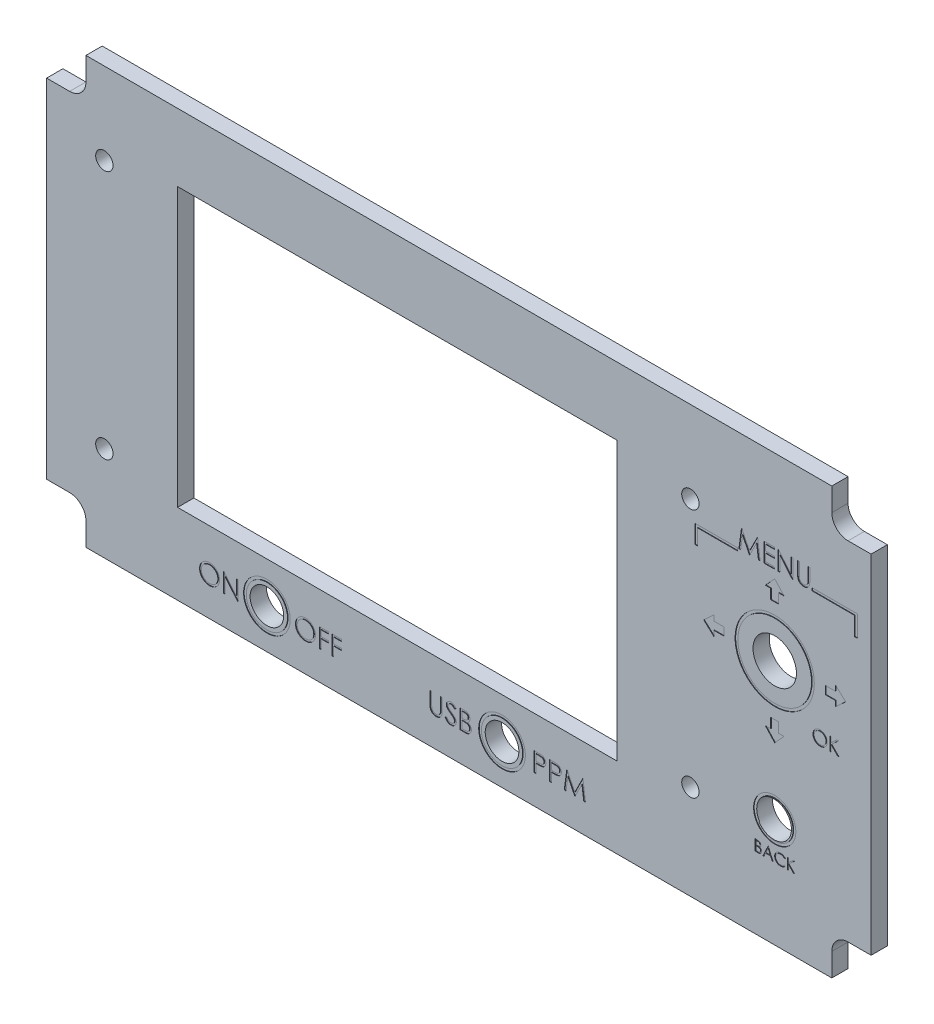
SolidWorks part; units mm, degrees
ref_plane "Plan de face" through (0, 0, 0) normal (0, 0, 1) x (1, 0, 0)
ref_plane "Plan de dessus" through (0, 0, 0) normal (0, 1, 0) x (1, 0, 0)
ref_plane "Plan de droite" through (0, 0, 0) normal (1, 0, 0) x (0, 0, -1)
sketch "Esquisse1" plane through (0, 0, 3.8) normal (0, 0, 1) x (1, 0, 0)
  line L0 (-95.6944, -23.7786) -> (-14.6944, -23.7786) construction
  line L1 (-14.6944, -23.7786) -> (-14.6944, 27.4214) construction
  line L2 (-108.6086, -31.3167) -> (5.0728, -31.3167) construction
  line L3 (-95.6944, 27.4214) -> (-95.6944, -23.7786) construction
  line L4 (-95.6944, -23.7786) -> (-14.6944, -23.7786)
  line L5 (-14.6944, -23.7786) -> (-14.6944, 27.4214)
  line L6 (-14.6944, 27.4214) -> (-95.6944, 27.4214)
  line L7 (-95.6944, 27.4214) -> (-95.6944, -23.7786)
  line L12 (32.1075, 39.9055) -> (-119.8323, 39.9055) construction
  line L13 (32.1075, -38.6114) -> (32.1075, 39.9055) construction
  line L15 (-119.8323, 39.9055) -> (-119.8323, -38.6114) construction
  line L24 (-115.5896, 32.6629) -> (-119.8323, 32.6629)
  line L25 (-119.8323, 32.6629) -> (-119.8323, -31.3687)
  line L26 (-119.8323, -31.3687) -> (-115.5896, -31.3687)
  line L27 (-112.5896, -34.3687) -> (-112.5896, -38.6114)
  line L28 (-112.5896, -38.6114) -> (24.8649, -38.6114)
  line L29 (24.8649, -38.6114) -> (24.8649, -34.3687)
  line L30 (27.8649, -31.3687) -> (32.1075, -31.3687)
  line L31 (32.1075, -31.3687) -> (32.1075, 32.6629)
  line L32 (32.1075, 32.6629) -> (27.8649, 32.6629)
  line L33 (24.8649, 35.6629) -> (24.8649, 39.9055)
  line L34 (24.8649, 39.9055) -> (-112.5896, 39.9055)
  line L35 (-112.5896, 39.9055) -> (-112.5896, 35.6629)
  circle A0 centre (-35.9056, -31.3167) radius 3.1
  circle A1 centre (-1.1944, 24.8214) radius 1.6
  circle A2 centre (-109.1944, 24.8214) radius 1.6
  circle A3 centre (-109.1944, -21.1786) radius 1.6
  circle A4 centre (-79.2375, -31.3167) radius 3.1
  circle A5 centre (-1.1944, -21.1786) radius 1.6
  circle A6 centre (-109.1944, 24.8214) radius 2 construction
  circle A7 centre (-1.1944, 24.8214) radius 2 construction
  arc A8 (-115.5896, 32.6629) -> (-112.5896, 35.6629) centre (-115.5896, 35.6629) ccw
  arc A9 (-112.5896, -34.3687) -> (-115.5896, -31.3687) centre (-115.5896, -34.3687) ccw
  arc A10 (27.8649, -31.3687) -> (24.8649, -34.3687) centre (27.8649, -34.3687) ccw
  arc A11 (24.8649, 35.6629) -> (27.8649, 32.6629) centre (27.8649, 35.6629) ccw
  circle A12 centre (-1.1944, -21.1786) radius 2 construction
  circle A13 centre (-109.1944, -21.1786) radius 2 construction
  circle A28 centre (14.3452, 6.7499) radius 4
  circle A45 centre (14.1766, -18.6114) radius 3.25
  dimension "D2" = 6.5
  dimension "D1" = 6.2
extrude "Boss.-Extru.1" add sketch "Esquisse1" along normal blind 3
sketch "Gravure" plane through (0, 0, 6.8) normal (0, 0, 1) x (1, 0, 0)
  line L0 (-0.3763, 21.3599) -> (-0.3763, 17.9616)
  line L1 (14.3452, 6.7499) -> (14.3452, 16.1393) construction
  line L2 (13.6084, 16.1393) -> (15.082, 16.1393)
  line L3 (13.6084, 16.1393) -> (13.6084, 17.9616)
  line L4 (13.6084, 17.9616) -> (12.6237, 17.9616)
  line L5 (12.6237, 17.9616) -> (14.3452, 19.8356)
  line L6 (14.3452, 19.8356) -> (16.0668, 17.9616)
  line L7 (16.0668, 17.9616) -> (15.082, 17.9616)
  line L8 (15.082, 17.9616) -> (15.082, 16.1393)
  line L9 (14.3452, 6.7499) -> (17.3937, 6.7499) construction
  line L10 (25.557, 6.013) -> (23.7347, 6.013)
  line L11 (25.557, 5.0283) -> (25.557, 6.013)
  line L12 (27.431, 6.7499) -> (25.557, 5.0283)
  line L13 (25.557, 8.4714) -> (27.431, 6.7499)
  line L14 (25.557, 7.4867) -> (25.557, 8.4714)
  line L15 (23.7347, 7.4867) -> (25.557, 7.4867)
  line L16 (23.7347, 7.4867) -> (23.7347, 6.013)
  line L17 (13.6084, -4.4619) -> (13.6084, -2.6396)
  line L18 (12.6237, -4.4619) -> (13.6084, -4.4619)
  line L19 (14.3452, -6.3359) -> (12.6237, -4.4619)
  line L20 (16.0668, -4.4619) -> (14.3452, -6.3359)
  line L21 (15.082, -4.4619) -> (16.0668, -4.4619)
  line L22 (15.082, -2.6396) -> (15.082, -4.4619)
  line L23 (15.082, -2.6396) -> (13.6084, -2.6396)
  line L24 (3.1335, 7.4867) -> (4.9558, 7.4867)
  line L25 (3.1335, 8.4714) -> (3.1335, 7.4867)
  line L26 (1.2595, 6.7499) -> (3.1335, 8.4714)
  line L27 (3.1335, 5.0283) -> (1.2595, 6.7499)
  line L28 (3.1335, 6.013) -> (3.1335, 5.0283)
  line L29 (4.9558, 6.013) -> (3.1335, 6.013)
  line L30 (4.9558, 6.013) -> (4.9558, 7.4867)
  line L31 (14.3452, 6.7499) -> (14.3452, -18.6114) construction
  line L32 (7.4858, 21.3599) -> (21.2046, 21.3599) construction
  line L33 (14.3452, 19.8356) -> (14.3452, 21.3599) construction
  line L34 (14.3452, -18.6114) -> (14.3452, -25.4203) construction
  line L35 (10.4971, -25.4203) -> (18.1934, -25.4203) construction
  line L36 (7.4858, 21.3599) -> (-0.3763, 21.3599)
  line L37 (-74.2371, -33.2481) -> (-67.4657, -33.2481) construction
  line L38 (21.2046, -2.6396) -> (25.557, -2.6396) construction
  line L39 (21.2046, 21.3599) -> (29.0668, 21.3599)
  line L40 (29.0668, 21.3599) -> (29.0668, 17.9616)
  line L41 (-91.913, -33.2481) -> (-84.8778, -33.2481) construction
  line L42 (-49.6295, -33.2481) -> (-41.3164, -33.2481) construction
  line L43 (-30.4453, -33.2481) -> (-24.3703, -33.2481) construction
  line L44 (7.4858, 20.8599) -> (0.1237, 20.8599)
  line L45 (0.1237, 20.8599) -> (0.1237, 17.9616)
  line L46 (21.2046, 21.8599) -> (29.5668, 21.8599)
  line L47 (29.5668, 21.8599) -> (29.5668, 17.9616)
  line L48 (-0.3763, 17.9616) -> (0.1237, 17.9616)
  line L49 (7.4858, 21.3599) -> (7.4858, 20.8599)
  line L50 (21.2046, 21.8599) -> (21.2046, 21.3599)
  line L51 (29.0668, 17.9616) -> (29.5668, 17.9616)
  circle A0 centre (14.3452, 6.7499) radius 6.7956
  circle A1 centre (14.3452, 6.7499) radius 7.2956
  circle A2 centre (-79.2375, -31.3167) radius 3.8
  circle A4 centre (14.3452, -18.6114) radius 3.3928
  circle A5 centre (14.3452, -18.6114) radius 3.8928
  circle A6 centre (-79.2375, -31.3167) radius 4.3
  circle A7 centre (-35.9056, -31.3167) radius 3.8
  circle A8 centre (-35.9056, -31.3167) radius 4.3
  text T0 "MENU"
  text T1 "BACK" font "Century Gothic" height 2
  text T2 "OK" font "Century Gothic" height 2.5
  text T3 "ON"
  text T4 "OFF"
  text T5 "USB"
  text T6 "PPM"
  point P7 (14.3452, 16.1393)
  point P38 (14.3452, 6.7499)
  point P39 (14.3452, 21.3599)
  point P45 (14.3452, -25.4203)
  dimension "D1" = 0.5
  dimension "D5" = 0.5
  dimension "D3" = 13
  dimension "D4" = 13
  dimension "D6" = 0.5
  dimension "D7" = 0.5
  dimension "D8" = 0.5
  dimension "D2" = 4
extrude "Enlèv. mat.-Extru.1" cut sketch "Gravure" against normal blind 0.1
